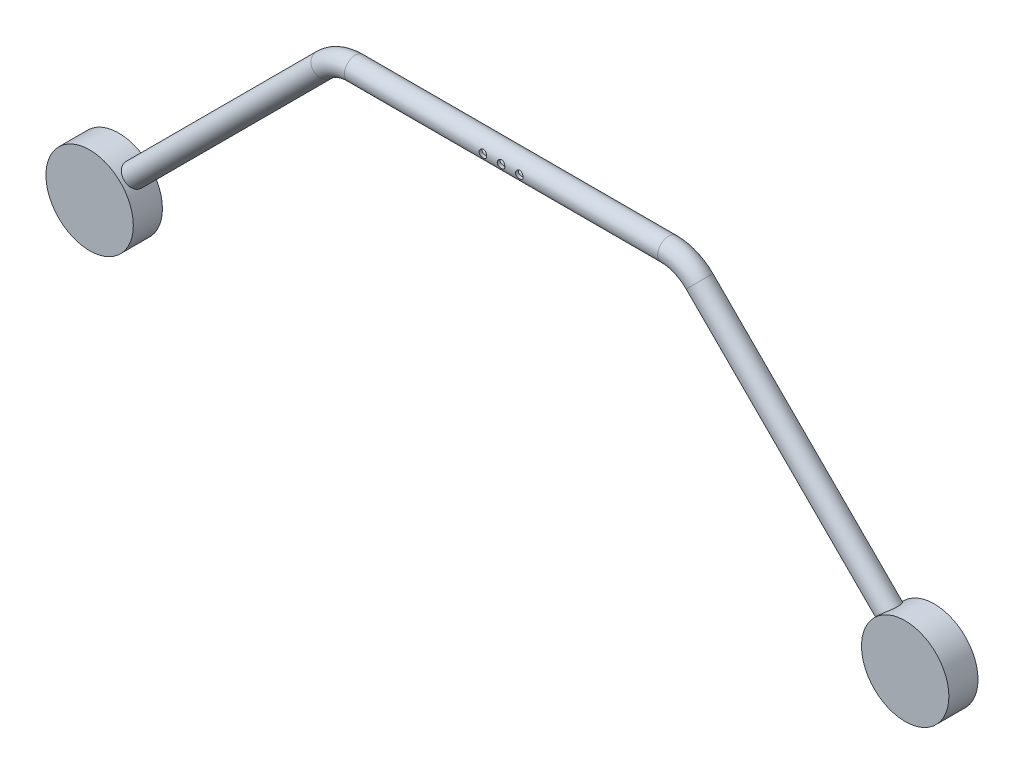
SolidWorks part; units mm, degrees
ref_plane "Front Plane" through (0, 0, 0) normal (0, 0, 1) x (1, 0, 0)
ref_plane "Top Plane" through (0, 0, 0) normal (0, 1, 0) x (1, 0, 0)
ref_plane "Right Plane" through (0, 0, 0) normal (1, 0, 0) x (0, 0, -1)
sketch "Sketch1" plane through (0, 0, 0) normal (0, 0, 1) x (1, 0, 0)
  line L10 (0, 19.4566) -> (0, -8.1997) construction
  line L11 (-355.6, -203.2) -> (-355.6, -165.1) construction
  line L12 (355.6, -203.2) -> (355.6, -165.1) construction
  circle A0 centre (-355.6, -203.2) radius 38.1
  circle A3 centre (-355.6, -203.2) radius 85.471 construction
  circle A4 centre (355.6, -203.2) radius 38.1
  circle A5 centre (355.6, -203.2) radius 85.471 construction
  point P16 (-355.6, -185.2)
  point P17 (355.6, -185.2)
  dimension "D5" = 76.2
  dimension "D6" = 170.942
  dimension "D4" = 18
  dimension "D7" = 18
  dimension "D8" = 711.2
  dimension "D1" = 203.2
extrude "Boss-Extrude1" add sketch "Sketch1" along normal blind 25.4 contours A0 | A4 | A0 | A4 region at (-355.6, -203.2, 0) region at (355.6, -203.2, 0)
ref_plane "Plane1" through (0, 0, 12.7) normal (0, 0, 1) x (1, 0, 0)
sketch "Sketch4" plane through (0, 0, 12.7) normal (0, 0, 1) x (1, 0, 0)
  line L0 (-355.6, -203.2) -> (-163.5592, -11.1592)
  line L1 (-136.6185, 0) -> (136.6185, 0)
  line L2 (163.5592, -11.1592) -> (355.6, -203.2)
  arc A0 (136.6185, 0) -> (163.5592, -11.1592) centre (136.6185, -38.1) cw
  arc A1 (-163.5592, -11.1592) -> (-136.6185, 0) centre (-136.6185, -38.1) cw
  point P5 (-232.6697, -120.1504)
  dimension "D1" = 38.1
  dimension "D2" = 711.2
  dimension "D3" = 203.2
  dimension "D4" = 135
sweep "Sweep1" add path "Sketch4" circular profile diameter 19.05 parameters "D3"=19.05
sketch "Sketch23" plane through (0, 0, 25.4) normal (0, 0, 1) x (1, 0, 0)
  line L0 (-15.875, 0) -> (15.875, 0) construction
  dimension "D1" = 31.75
shell "Shell1" thickness 2.54 removed face at (348.8648, -209.9352, 12.7) removed face at (-348.8648, -209.9352, 12.7)
hole_wizard "M6 Clearance Hole1" positions "3DSketch1" profile "Sketch49" hole size "M6" standard "ANSI Metric" end condition through all
sketch3d "3DSketch1"
  point P0 (-15.875, 0, 22.225)
  point P2 (15.875, 0, 22.225)
  point P6 (0, 0, 0)
  point P8 (0, 0, 0)
sketch "Sketch49" plane through (-15.875, 0, 22.225) normal (1, 0, 0) x (0, -1, 0)
  line L0 (0, 0) -> (0, 22.225)
  line L1 (0, 22.225) -> (3.3, 22.225)
  line L2 (3.3, 22.225) -> (3.3, 0.025)
  line L3 (3.3, 0.025) -> (3.325, 0)
  line L5 (3.325, 0) -> (0, 0)
  line L6 (-3.3, 0.025) -> (-3.325, 0) construction
  line L11 (0, -6.35) -> (0, 107.95) construction
  dimension "Thru Hole Dia." = 6.6
  dimension "Thru Hole Depth" = 22.225
  dimension "Near C'Sink Dia." = 6.65
  dimension "Near C'Sink Angle" = 90
hole_wizard "M6 Clearance Hole2" positions "3DSketch2" profile "Sketch51" hole size "M6" standard "ANSI Metric" end condition through all
sketch3d "3DSketch2"
  point P0 (0, 0, 22.225)
sketch "Sketch51" plane through (0, 0, 22.225) normal (1, 0, 0) x (0, -1, 0)
  line L0 (0, 0) -> (0, 22.225)
  line L1 (0, 22.225) -> (3.3, 22.225)
  line L2 (3.3, 22.225) -> (3.3, 0.025)
  line L3 (3.3, 0.025) -> (3.325, 0)
  line L5 (3.325, 0) -> (0, 0)
  line L6 (-3.3, 0.025) -> (-3.325, 0) construction
  line L11 (0, -6.35) -> (0, 107.95) construction
  dimension "Thru Hole Dia." = 6.6
  dimension "Thru Hole Depth" = 22.225
  dimension "Near C'Sink Dia." = 6.65
  dimension "Near C'Sink Angle" = 90
equation "\"Rover_Length\"= 25in"
equation "\"Rover_Width\"= 18in"
equation "\"Rover_Height\"= 12in"
equation "\"Chassis_Wheelbase\"= 28in"
equation "\"Chassis_WheelDiam\"= 171mm"
equation "\"Chassis_ArmDiamWidth\"= 0.75in"
equation "\"Chassis_ArmAngle\"= 135deg"
equation "\"Chassis_HubMountOD\"= 3in"
equation "\"Chassis_WheelBoltHole\"= 36mm"
equation "\"Chassis_WheelBoltNum\"= 4"
equation "\"Chassis_DiffBarLength\"= 12in"
equation "\"Chassis_DiffBarWidth\"= 1in"
equation "\"Chassis_DiffBarHeight\"= 0.5in"
equation "\"Chassis_DiffLinkage_Length\"= 2.5in"
equation "\"D5@Sketch1\"=\"Chassis_HubMountOD\""
equation "\"D4@Sketch1\"=\"Chassis_WheelBoltHole\"/2"
equation "\"D7@Sketch1\"=\"Chassis_WheelBoltHole\"/2"
equation "\"D8@Sketch1\"=\"Chassis_Wheelbase\""
equation "\"D1@Boss-Extrude1\"=\"Chassis_DiffBarWidth\""
equation "\"D2@Sketch4\"=\"Chassis_Wheelbase\""
equation "\"Chassis_ArmHeight\"= 8in"
equation "\"Chassis_MountBracketThickness\"= 0.125in"
equation "\"Chassis_MountBracketWidth\"= 3in"
equation "\"Chassis_MountBacketOverlap\"= 0.5in"
equation "\"Chassis_ArmShaftDiam\"= 0.75in"
equation "\"D3@Sketch4\"=\"Chassis_ArmHeight\""
equation "\"D4@Sketch4\"=\"Chassis_ArmAngle\""
equation "\"D1@Sketch1\"=\"Chassis_ArmHeight\""
equation "\"Chassis_ArmHoleSpacing\" = 1.25in"
equation "\"D1@Sketch23\"=\"Chassis_ArmHoleSpacing\""
